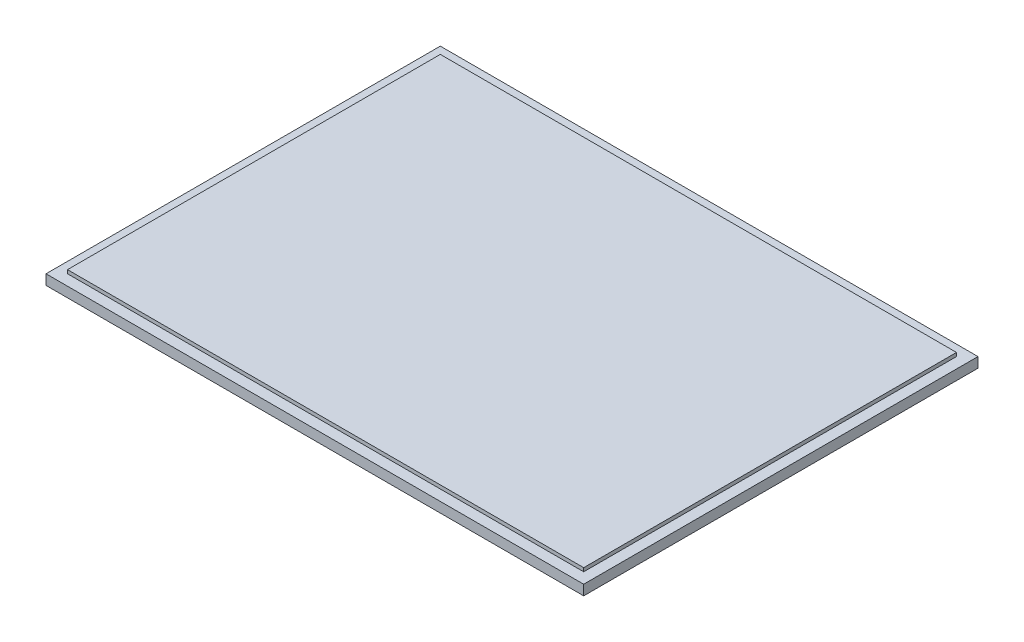
SolidWorks part; units mm, degrees
ref_plane "Front Plane" through (0, 0, 0) normal (0, 0, 1) x (1, 0, 0)
ref_plane "Top Plane" through (0, 0, 0) normal (0, 1, 0) x (1, 0, 0)
ref_plane "Right Plane" through (0, 0, 0) normal (1, 0, 0) x (0, 0, -1)
sketch "Sketch1" plane through (0, 0, 0) normal (0, 1, 0) x (1, 0, 0)
  line L0 (-375, 275) -> (375, 275)
  line L1 (-380, -280) -> (380, -280) construction
  line L2 (-380, -280) -> (-380, 280) construction
  line L3 (-380, 280) -> (380, 280) construction
  line L4 (380, -280) -> (380, 280) construction
  line L5 (-380, -280) -> (380, 280) construction
  line L6 (-380, 280) -> (380, -280) construction
  line L7 (375, -275) -> (375, 275)
  line L8 (-375, -275) -> (375, -275)
  line L9 (-375, -275) -> (-375, 275)
  point P0 (0, 0)
  dimension "D1" = 760
  dimension "D2" = 560
  dimension "D3" = 5
extrude "Boss-Extrude1" add sketch "Sketch1" along normal blind 19.1
sketch "Sketch2" plane through (0, 19.1, 0) normal (0, 1, 0) x (1, 0, 0)
  line L0 (375, 275) -> (-375, 275) construction
  line L5 (-370, 0) -> (370, 0) construction
  line L7 (-370, -270) -> (370, -270) construction
  line L8 (-370, -270) -> (-370, 270) construction
  line L9 (-370, 270) -> (370, 270) construction
  line L10 (370, -270) -> (370, 270) construction
  line L11 (-370, -270) -> (370, 270) construction
  line L12 (-370, 270) -> (370, -270) construction
  line L13 (375, -275) -> (375, 275) construction
  line L14 (0, 270) -> (0, -270) construction
  circle A1 centre (-370, 270) radius 1.5
  circle A2 centre (-185, 270) radius 1.5
  circle A3 centre (0, 270) radius 1.5
  circle A4 centre (185, 270) radius 1.5
  circle A5 centre (370, 270) radius 1.5
  circle A6 centre (-370, 90) radius 1.5
  circle A7 centre (-370, -90) radius 1.5
  circle A8 centre (-370, -270) radius 1.5
  circle A9 centre (370, -270) radius 1.5
  circle A10 centre (185, -270) radius 1.5
  circle A11 centre (0, -270) radius 1.5
  circle A12 centre (-185, -270) radius 1.5
  circle A13 centre (-370, -270) radius 1.5
  circle A14 centre (370, -90) radius 1.5
  circle A15 centre (370, 90) radius 1.5
  point P0 (0, 0)
  point P6 (0, 0)
  dimension "D1" = 3
  dimension "D2" = 5
  dimension "D3" = 5
  dimension "D4" = 5
  dimension "D5" = 4
extrude "Cut-Extrude1" [suppressed] cut sketch "Sketch2" against normal through all contours A1 | A2 | A3 | A4 | A5 | A15 | A14 | A9 | A10 | A11 | A12 | A8 | A7 | A6
sketch "Sketch3" plane through (0, 19.1, 0) normal (0, 1, 0) x (1, 0, 0)
  line L8 (-360, 260) -> (-360, -260)
  line L9 (-360, -260) -> (360, -260)
  line L10 (360, -260) -> (360, 260)
  line L11 (360, 260) -> (-360, 260)
  line L12 (-360, 260) -> (-360, -260)
  line L13 (-360, -260) -> (360, -260)
  line L14 (360, -260) -> (360, 260)
  line L15 (360, 260) -> (-360, 260)
  line L16 (-375, 275) -> (-375, -275)
  line L17 (-375, -275) -> (375, -275)
  line L18 (375, -275) -> (375, 275)
  line L19 (375, 275) -> (-375, 275)
  line L20 (-375, 275) -> (-375, -275)
  line L21 (-375, -275) -> (375, -275)
  line L22 (375, -275) -> (375, 275)
  line L23 (375, 275) -> (-375, 275)
  dimension "D1" = 15
  dimension "D2" = 0
extrude "Cut-Extrude2" cut sketch "Sketch3" against normal blind 5
equation "\"Crossbar_Width\"= 80mm"
equation "\"Vertical_Offset\"= \"Crossbar_Width\" / 2"
equation "\"Toolhead_Width\"= 100mm"
equation "\"Mechanical_Buffer\"= 30mm"
equation "\"Z_Interstitial\"= 100mm"
equation "\"Z_Interstitial_Sketch\"= \"Z_Interstitial\" + 1in"
